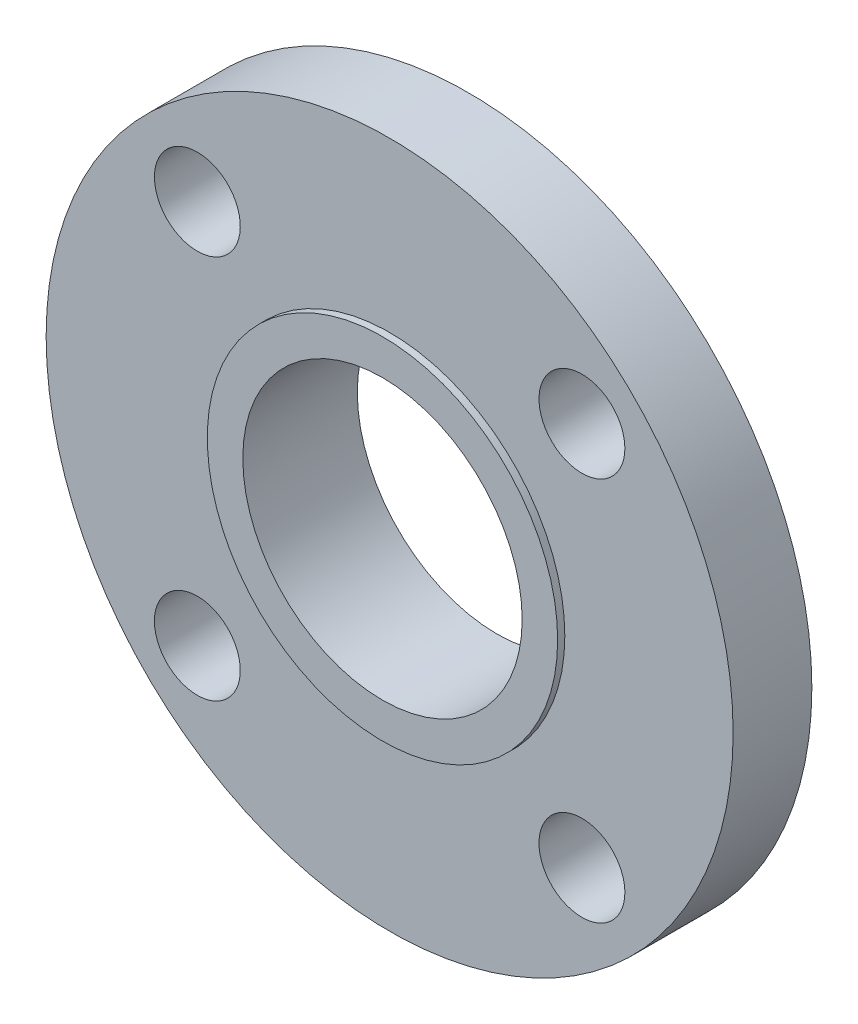
SolidWorks part; units mm, degrees
ref_plane "front" through (0, 0, 0) normal (0, 0, 1) x (1, 0, 0)
ref_plane "top" through (0, 0, 0) normal (0, 1, 0) x (1, 0, 0)
ref_plane "side" through (0, 0, 0) normal (1, 0, 0) x (0, 0, -1)
other "Configuration Table"
sketch "Hub Diameter" plane through (0, 0, 0) normal (0, 0, 1) x (1, 0, 0)
  circle A0 centre (0, 0) radius 38.862
  dimension "Diameter of Hub X" = 77.724
extrude "Hub" add sketch "Hub Diameter" against normal blind 25.4
ref_plane "Flange starting plane" through (0, 0, -1.5875) normal (0, 0, 1) x (1, 0, 0)
ref_plane "Flange end plane" through (0, 0, -19.05) normal (0, 0, 1) x (1, 0, 0)
sketch "Flange Diameter" plane through (0, 0, -1.5875) normal (0, 0, 1) x (1, 0, 0)
  circle A0 centre (0, 0) radius 76.2
  dimension "Outside Diameter of Flange O" = 152.4
extrude "Flange" add sketch "Flange Diameter" against normal up to surface (17.4625 mm away) up to plane "Flange end plane"
ref_axis "Axis of Revolution for Bore" through (0, 0, -50) along (0, 0, 1)
sketch "Bolt Diameter" plane through (0, 0, -1.5875) normal (0, 0, 1) x (1, 0, 0)
  line L0 (0, 19.05) -> (0, -19.05) construction
  line L1 (17.2244, 17.2244) -> (-17.2244, -17.2244) construction
  circle A0 centre (42.6562, 42.6562) radius 9.525
  circle A1 centre (0, 0) radius 60.325 construction
  point P0 (0, 0)
  dimension "Diameter of Bolt Holes" = 19.05
  dimension "Diameter of Bolt Circle" = 120.65
  dimension "Angle" = 45
sketch "Revolution profile for Bore" plane through (0, 0, 0) normal (0, 1, 0) x (1, 0, 0)
  line L0 (0, -19.5213) -> (0, 228.6) construction
  line L1 (0, 1.5875) -> (0, 0) construction
  line L2 (0, 0) -> (30.988, 0)
  line L3 (30.988, 0) -> (30.988, 228.6)
  line L4 (30.988, 228.6) -> (0, 228.6)
  line L5 (0, 228.6) -> (0, 0)
  point P4 (0, 0)
  dimension "D2" = 61.976
  dimension "Hub Length Y" = 228.6
revolve "Bore" cut sketch "Revolution profile for Bore" angle 360 about L0
extrude "Bolt Hole" cut sketch "Bolt Diameter" against normal through all
pattern_circular "Bolt Hole Pattern" count 4 every 90 about axis through (0, 0, -50) along (0, 0, 1) of "Bolt Hole"
sketch "Sketch1" plane through (0, 0, 0) normal (0, 1, 0) x (1, 0, 0)
  line L1 (0, -19.5213) -> (0, 228.6) construction
  line L2 (-30.988, 0) -> (30.988, 0) construction
  point P0 (0, 6.35)
  point P6 (0, 0)
  dimension "D1" = 6.35
other "CPoint1" parameters "Diameter"=50.8, "StubLength"=0
ref_axis "Axis1" through (0, 0, -16.35) along (0, 0, 1)
other "RPoint1"
ref_axis "Axis of Rotation" through (0, 0, -25.4) along (0, 0, 1)
ref_axis "Vertical" through (0, 0, -6.35) along (0, 1, 0)
equation "\"flange height@Flange starting plane\" =  ( \"Hub Length Y@Hub\" - \"Thickness of Flange C@Flange end plane\" )  / 3"
equation "\"angular position of Bolt Holes@Bolt Hole Pattern\" = 360/\"Number of Bolt Holes@Bolt Hole Pattern\""
